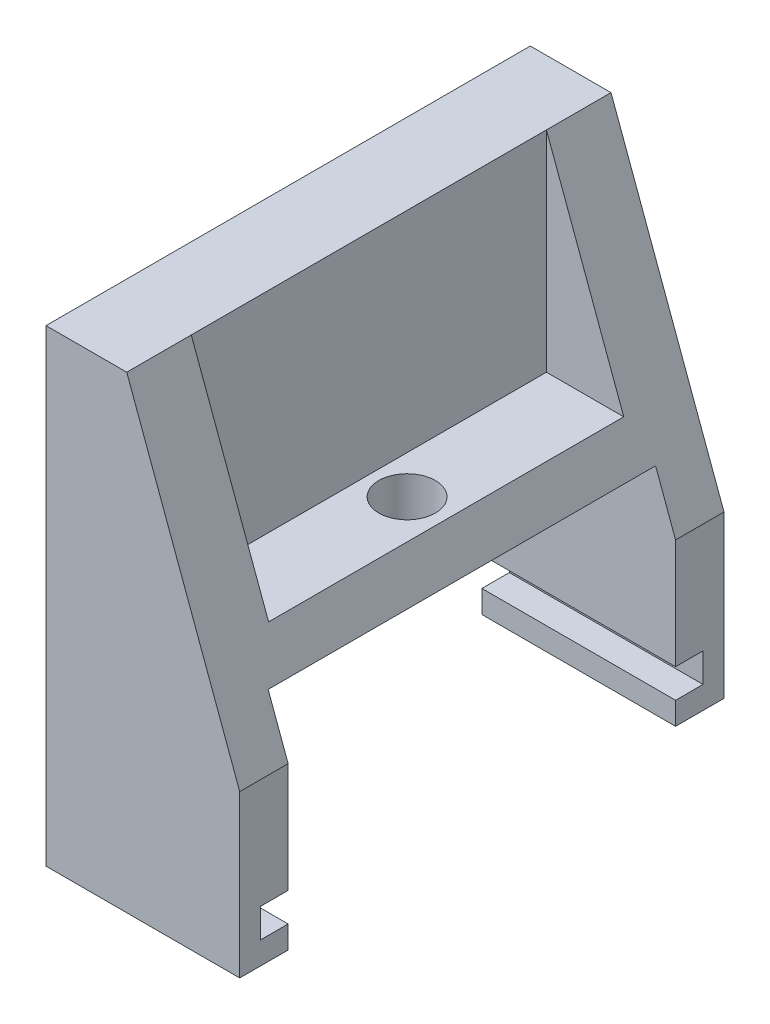
SolidWorks part; units mm, degrees
ref_plane "Front Plane" through (0, 0, 0) normal (0, 0, 1) x (1, 0, 0)
ref_plane "Top Plane" through (0, 0, 0) normal (0, 1, 0) x (1, 0, 0)
ref_plane "Right Plane" through (0, 0, 0) normal (1, 0, 0) x (0, 0, -1)
sketch "Sketch1" plane through (0, 0, 0) normal (0, 0, 1) x (1, 0, 0)
  line L0 (0, 0) -> (0, -29)
  line L1 (0, -29) -> (12, -29)
  line L2 (12, -29) -> (12, -19)
  line L3 (12, -19) -> (5, 0)
  line L4 (5, 0) -> (0, 0)
  dimension "D1" = 29
  dimension "D2" = 12
  dimension "D3" = 10
  dimension "D4" = 5
extrude "Boss-Extrude1" add sketch "Sketch1" against normal blind 30
sketch "Sketch4" plane through (0, 0, 0) normal (-1, 0, 0) x (0, 0, 1)
  line L0 (-30, 0) -> (-30, -29) construction
  line L1 (-27, -15.6386) -> (-3, -15.6386)
  line L2 (-27, -15.6386) -> (-27, -29.6386)
  line L3 (-27, -29.6386) -> (-3, -29.6386)
  line L4 (-3, -15.6386) -> (-3, -29.6386)
  point P4 (-27, -22.6386)
  point P7 (-27, -27.5631)
  dimension "D1" = 24
  dimension "D2" = 14
  dimension "D3" = 3
extrude "Cut-Extrude2" cut sketch "Sketch4" against normal blind 25 contours L2 L1 L4 L3
sketch "Sketch5" plane through (0, 0, 0) normal (-1, 0, 0) x (0, 0, 1)
  line L0 (-3, -15.6386) -> (-3, -29) construction
  line L1 (-3, -25.8) -> (-1.3, -25.8)
  line L2 (-3, -25.8) -> (-3, -27.6)
  line L3 (-3, -27.6) -> (-1.3, -27.6)
  line L4 (-1.3, -25.8) -> (-1.3, -27.6)
  line L5 (-3, -29) -> (0, -29) construction
  dimension "D1" = 1.8
  dimension "D2" = 1.7
  dimension "D3" = 1.4
extrude "Cut-Extrude3" cut sketch "Sketch5" against normal blind 15
ref_plane "Plane1" through (0, 0, -15) normal (0, 0, 1) x (1, 0, 0)
mirror "Mirror1" about plane through (0, 0, -15) normal (0, 0, 1) of "Cut-Extrude3"
sketch "Sketch6" plane through (0, 0, -15) normal (0, 0, 1) x (1, 0, 0)
  line L0 (5, 0) -> (5, -13)
  line L1 (5, -13) -> (9.7895, -13)
  line L2 (12, -19) -> (5, 0) construction
  line L3 (9.7895, -13) -> (5, 0)
  dimension "D1" = 13
extrude "Cut-Extrude4" cut sketch "Sketch6" against normal mid plane 22
sketch "Sketch7" plane through (0, -13, 0) normal (0, 1, 0) x (1, 0, 0)
  line L0 (-6.6, 15) -> (6.6, 15) construction
  circle A0 centre (7.3667, 15) radius 1.75
  point P4 (7.3667, 15)
  dimension "D1" = 3.5
extrude "Cut-Extrude5" cut sketch "Sketch7" against normal blind 4 contours A0
